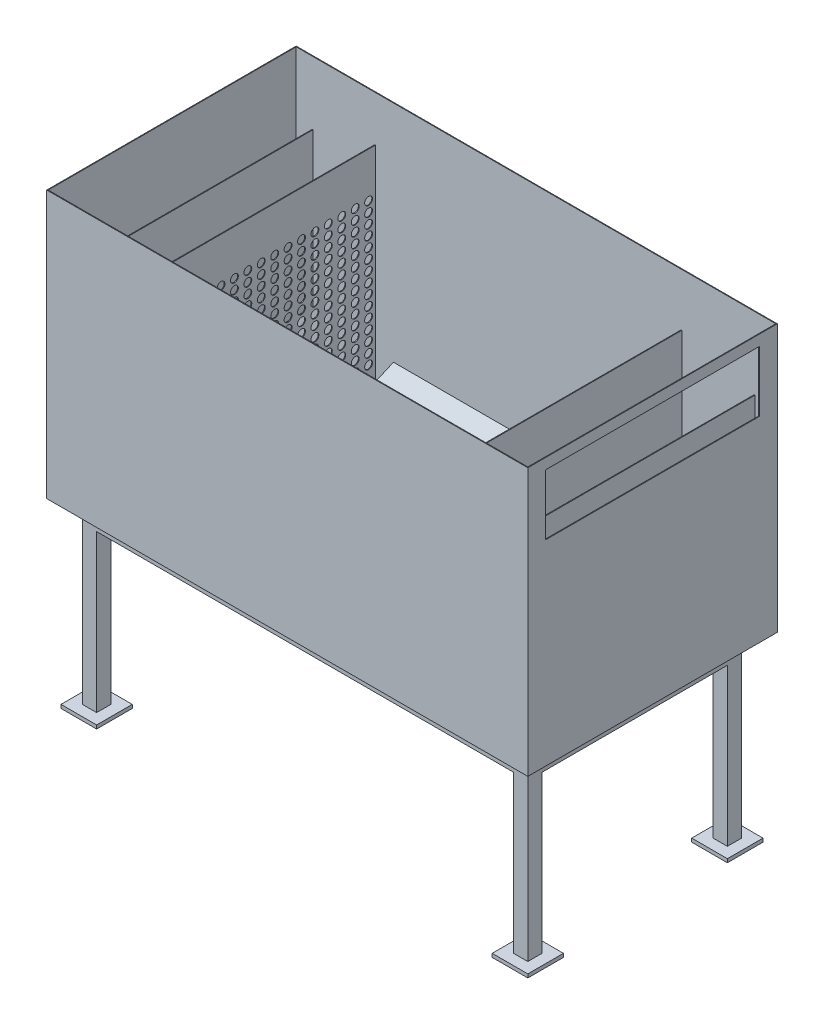
SolidWorks part; units mm, degrees
ref_plane "Спереди" through (0, 0, 0) normal (0, 0, 1) x (1, 0, 0)
ref_plane "Сверху" through (0, 0, 0) normal (0, 1, 0) x (1, 0, 0)
ref_plane "Справа" through (0, 0, 0) normal (1, 0, 0) x (0, 0, -1)
sketch "MASTER_FOOTPRINT" plane through (0, 0, 0) normal (0, 1, 0) x (1, 0, 0)
  line L1 (0, 0) -> (1350, 0)
  line L2 (0, 0) -> (0, 700)
  line L3 (0, 700) -> (1350, 700)
  line L4 (1350, 0) -> (1350, 700)
  dimension "D1" = 1350
  dimension "D2" = 700
extrude "BATH_BASE_PLATE" add sketch "MASTER_FOOTPRINT" along normal blind 750
shell "BATH_SHELL_2MM" thickness 2 removed face at (675, 750, -350)
sketch "Эскиз1" plane through (0, 0, 0) normal (1, 0, 0) x (0, 0, -1)
  circle A0 centre (350, 420) radius 50
extrude "INLET_D100_OPENING" cut sketch "Эскиз1" along normal blind 10
sketch "Эскиз2" plane through (0, 0, 0) normal (1, 0, 0) x (0, 0, -1)
  line L1 (80, 220) -> (620, 220)
  line L2 (80, 220) -> (80, 650)
  line L3 (80, 650) -> (620, 650)
  line L4 (620, 220) -> (620, 650)
extrude "INLET_IMPACT_BAFFLE" add sketch "Эскиз2" along normal blind 2 from offset 125 separate body
sketch "Эскиз3" plane through (0, 0, 0) normal (1, 0, 0) x (0, 0, -1)
  line L1 (30, 2) -> (670, 2)
  line L2 (30, 2) -> (30, 650)
  line L3 (30, 650) -> (670, 650)
  line L4 (670, 2) -> (670, 650)
  circle A0 centre (48.8235, 125) radius 11
  circle A1 centre (48.8235, 153.5) radius 11
  circle A2 centre (48.8235, 182) radius 11
  circle A3 centre (48.8235, 210.5) radius 11
  circle A4 centre (48.8235, 239) radius 11
  circle A5 centre (48.8235, 267.5) radius 11
  circle A6 centre (48.8235, 296) radius 11
  circle A7 centre (48.8235, 324.5) radius 11
  circle A8 centre (48.8235, 353) radius 11
  circle A9 centre (48.8235, 381.5) radius 11
  circle A10 centre (48.8235, 410) radius 11
  circle A11 centre (48.8235, 438.5) radius 11
  circle A12 centre (48.8235, 467) radius 11
  circle A13 centre (48.8235, 495.5) radius 11
  circle A14 centre (48.8235, 524) radius 11
  circle A15 centre (86.4706, 125) radius 11
  circle A16 centre (86.4706, 153.5) radius 11
  circle A17 centre (86.4706, 182) radius 11
  circle A18 centre (86.4706, 210.5) radius 11
  circle A19 centre (86.4706, 239) radius 11
  circle A20 centre (86.4706, 267.5) radius 11
  circle A21 centre (86.4706, 296) radius 11
  circle A22 centre (86.4706, 324.5) radius 11
  circle A23 centre (86.4706, 353) radius 11
  circle A24 centre (86.4706, 381.5) radius 11
  circle A25 centre (86.4706, 410) radius 11
  circle A26 centre (86.4706, 438.5) radius 11
  circle A27 centre (86.4706, 467) radius 11
  circle A28 centre (86.4706, 495.5) radius 11
  circle A29 centre (86.4706, 524) radius 11
  circle A30 centre (124.1176, 125) radius 11
  circle A31 centre (124.1176, 153.5) radius 11
  circle A32 centre (124.1176, 182) radius 11
  circle A33 centre (124.1176, 210.5) radius 11
  circle A34 centre (124.1176, 239) radius 11
  circle A35 centre (124.1176, 267.5) radius 11
  circle A36 centre (124.1176, 296) radius 11
  circle A37 centre (124.1176, 324.5) radius 11
  circle A38 centre (124.1176, 353) radius 11
  circle A39 centre (124.1176, 381.5) radius 11
  circle A40 centre (124.1176, 410) radius 11
  circle A41 centre (124.1176, 438.5) radius 11
  circle A42 centre (124.1176, 467) radius 11
  circle A43 centre (124.1176, 495.5) radius 11
  circle A44 centre (124.1176, 524) radius 11
  circle A45 centre (161.7647, 125) radius 11
  circle A46 centre (161.7647, 153.5) radius 11
  circle A47 centre (161.7647, 182) radius 11
  circle A48 centre (161.7647, 210.5) radius 11
  circle A49 centre (161.7647, 239) radius 11
  circle A50 centre (161.7647, 267.5) radius 11
  circle A51 centre (161.7647, 296) radius 11
  circle A52 centre (161.7647, 324.5) radius 11
  circle A53 centre (161.7647, 353) radius 11
  circle A54 centre (161.7647, 381.5) radius 11
  circle A55 centre (161.7647, 410) radius 11
  circle A56 centre (161.7647, 438.5) radius 11
  circle A57 centre (161.7647, 467) radius 11
  circle A58 centre (161.7647, 495.5) radius 11
  circle A59 centre (161.7647, 524) radius 11
  circle A60 centre (199.4118, 125) radius 11
  circle A61 centre (199.4118, 153.5) radius 11
  circle A62 centre (199.4118, 182) radius 11
  circle A63 centre (199.4118, 210.5) radius 11
  circle A64 centre (199.4118, 239) radius 11
  circle A65 centre (199.4118, 267.5) radius 11
  circle A66 centre (199.4118, 296) radius 11
  circle A67 centre (199.4118, 324.5) radius 11
  circle A68 centre (199.4118, 353) radius 11
  circle A69 centre (199.4118, 381.5) radius 11
  circle A70 centre (199.4118, 410) radius 11
  circle A71 centre (199.4118, 438.5) radius 11
  circle A72 centre (199.4118, 467) radius 11
  circle A73 centre (199.4118, 495.5) radius 11
  circle A74 centre (199.4118, 524) radius 11
  circle A75 centre (237.0588, 125) radius 11
  circle A76 centre (237.0588, 153.5) radius 11
  circle A77 centre (237.0588, 182) radius 11
  circle A78 centre (237.0588, 210.5) radius 11
  circle A79 centre (237.0588, 239) radius 11
  circle A80 centre (237.0588, 267.5) radius 11
  circle A81 centre (237.0588, 296) radius 11
  circle A82 centre (237.0588, 324.5) radius 11
  circle A83 centre (237.0588, 353) radius 11
  circle A84 centre (237.0588, 381.5) radius 11
  circle A85 centre (237.0588, 410) radius 11
  circle A86 centre (237.0588, 438.5) radius 11
  circle A87 centre (237.0588, 467) radius 11
  circle A88 centre (237.0588, 495.5) radius 11
  circle A89 centre (237.0588, 524) radius 11
  circle A90 centre (274.7059, 125) radius 11
  circle A91 centre (274.7059, 153.5) radius 11
  circle A92 centre (274.7059, 182) radius 11
  circle A93 centre (274.7059, 210.5) radius 11
  circle A94 centre (274.7059, 239) radius 11
  circle A95 centre (274.7059, 267.5) radius 11
  circle A96 centre (274.7059, 296) radius 11
  circle A97 centre (274.7059, 324.5) radius 11
  circle A98 centre (274.7059, 353) radius 11
  circle A99 centre (274.7059, 381.5) radius 11
  circle A100 centre (274.7059, 410) radius 11
  circle A101 centre (274.7059, 438.5) radius 11
  circle A102 centre (274.7059, 467) radius 11
  circle A103 centre (274.7059, 495.5) radius 11
  circle A104 centre (274.7059, 524) radius 11
  circle A105 centre (312.3529, 125) radius 11
  circle A106 centre (312.3529, 153.5) radius 11
  circle A107 centre (312.3529, 182) radius 11
  circle A108 centre (312.3529, 210.5) radius 11
  circle A109 centre (312.3529, 239) radius 11
  circle A110 centre (312.3529, 267.5) radius 11
  circle A111 centre (312.3529, 296) radius 11
  circle A112 centre (312.3529, 324.5) radius 11
  circle A113 centre (312.3529, 353) radius 11
  circle A114 centre (312.3529, 381.5) radius 11
  circle A115 centre (312.3529, 410) radius 11
  circle A116 centre (312.3529, 438.5) radius 11
  circle A117 centre (312.3529, 467) radius 11
  circle A118 centre (312.3529, 495.5) radius 11
  circle A119 centre (312.3529, 524) radius 11
  circle A120 centre (350, 125) radius 11
  circle A121 centre (350, 153.5) radius 11
  circle A122 centre (350, 182) radius 11
  circle A123 centre (350, 210.5) radius 11
  circle A124 centre (350, 239) radius 11
  circle A125 centre (350, 267.5) radius 11
  circle A126 centre (350, 296) radius 11
  circle A127 centre (350, 324.5) radius 11
  circle A128 centre (350, 353) radius 11
  circle A129 centre (350, 381.5) radius 11
  circle A130 centre (350, 410) radius 11
  circle A131 centre (350, 438.5) radius 11
  circle A132 centre (350, 467) radius 11
  circle A133 centre (350, 495.5) radius 11
  circle A134 centre (350, 524) radius 11
  circle A135 centre (387.6471, 125) radius 11
  circle A136 centre (387.6471, 153.5) radius 11
  circle A137 centre (387.6471, 182) radius 11
  circle A138 centre (387.6471, 210.5) radius 11
  circle A139 centre (387.6471, 239) radius 11
  circle A140 centre (387.6471, 267.5) radius 11
  circle A141 centre (387.6471, 296) radius 11
  circle A142 centre (387.6471, 324.5) radius 11
  circle A143 centre (387.6471, 353) radius 11
  circle A144 centre (387.6471, 381.5) radius 11
  circle A145 centre (387.6471, 410) radius 11
  circle A146 centre (387.6471, 438.5) radius 11
  circle A147 centre (387.6471, 467) radius 11
  circle A148 centre (387.6471, 495.5) radius 11
  circle A149 centre (387.6471, 524) radius 11
  circle A150 centre (425.2941, 125) radius 11
  circle A151 centre (425.2941, 153.5) radius 11
  circle A152 centre (425.2941, 182) radius 11
  circle A153 centre (425.2941, 210.5) radius 11
  circle A154 centre (425.2941, 239) radius 11
  circle A155 centre (425.2941, 267.5) radius 11
  circle A156 centre (425.2941, 296) radius 11
  circle A157 centre (425.2941, 324.5) radius 11
  circle A158 centre (425.2941, 353) radius 11
  circle A159 centre (425.2941, 381.5) radius 11
  circle A160 centre (425.2941, 410) radius 11
  circle A161 centre (425.2941, 438.5) radius 11
  circle A162 centre (425.2941, 467) radius 11
  circle A163 centre (425.2941, 495.5) radius 11
  circle A164 centre (425.2941, 524) radius 11
  circle A165 centre (462.9412, 125) radius 11
  circle A166 centre (462.9412, 153.5) radius 11
  circle A167 centre (462.9412, 182) radius 11
  circle A168 centre (462.9412, 210.5) radius 11
  circle A169 centre (462.9412, 239) radius 11
  circle A170 centre (462.9412, 267.5) radius 11
  circle A171 centre (462.9412, 296) radius 11
  circle A172 centre (462.9412, 324.5) radius 11
  circle A173 centre (462.9412, 353) radius 11
  circle A174 centre (462.9412, 381.5) radius 11
  circle A175 centre (462.9412, 410) radius 11
  circle A176 centre (462.9412, 438.5) radius 11
  circle A177 centre (462.9412, 467) radius 11
  circle A178 centre (462.9412, 495.5) radius 11
  circle A179 centre (462.9412, 524) radius 11
  circle A180 centre (500.5882, 125) radius 11
  circle A181 centre (500.5882, 153.5) radius 11
  circle A182 centre (500.5882, 182) radius 11
  circle A183 centre (500.5882, 210.5) radius 11
  circle A184 centre (500.5882, 239) radius 11
  circle A185 centre (500.5882, 267.5) radius 11
  circle A186 centre (500.5882, 296) radius 11
  circle A187 centre (500.5882, 324.5) radius 11
  circle A188 centre (500.5882, 353) radius 11
  circle A189 centre (500.5882, 381.5) radius 11
  circle A190 centre (500.5882, 410) radius 11
  circle A191 centre (500.5882, 438.5) radius 11
  circle A192 centre (500.5882, 467) radius 11
  circle A193 centre (500.5882, 495.5) radius 11
  circle A194 centre (500.5882, 524) radius 11
  circle A195 centre (538.2353, 125) radius 11
  circle A196 centre (538.2353, 153.5) radius 11
  circle A197 centre (538.2353, 182) radius 11
  circle A198 centre (538.2353, 210.5) radius 11
  circle A199 centre (538.2353, 239) radius 11
  circle A200 centre (538.2353, 267.5) radius 11
  circle A201 centre (538.2353, 296) radius 11
  circle A202 centre (538.2353, 324.5) radius 11
  circle A203 centre (538.2353, 353) radius 11
  circle A204 centre (538.2353, 381.5) radius 11
  circle A205 centre (538.2353, 410) radius 11
  circle A206 centre (538.2353, 438.5) radius 11
  circle A207 centre (538.2353, 467) radius 11
  circle A208 centre (538.2353, 495.5) radius 11
  circle A209 centre (538.2353, 524) radius 11
  circle A210 centre (575.8824, 125) radius 11
  circle A211 centre (575.8824, 153.5) radius 11
  circle A212 centre (575.8824, 182) radius 11
  circle A213 centre (575.8824, 210.5) radius 11
  circle A214 centre (575.8824, 239) radius 11
  circle A215 centre (575.8824, 267.5) radius 11
  circle A216 centre (575.8824, 296) radius 11
  circle A217 centre (575.8824, 324.5) radius 11
  circle A218 centre (575.8824, 353) radius 11
  circle A219 centre (575.8824, 381.5) radius 11
  circle A220 centre (575.8824, 410) radius 11
  circle A221 centre (575.8824, 438.5) radius 11
  circle A222 centre (575.8824, 467) radius 11
  circle A223 centre (575.8824, 495.5) radius 11
  circle A224 centre (575.8824, 524) radius 11
  circle A225 centre (613.5294, 125) radius 11
  circle A226 centre (613.5294, 153.5) radius 11
  circle A227 centre (613.5294, 182) radius 11
  circle A228 centre (613.5294, 210.5) radius 11
  circle A229 centre (613.5294, 239) radius 11
  circle A230 centre (613.5294, 267.5) radius 11
  circle A231 centre (613.5294, 296) radius 11
  circle A232 centre (613.5294, 324.5) radius 11
  circle A233 centre (613.5294, 353) radius 11
  circle A234 centre (613.5294, 381.5) radius 11
  circle A235 centre (613.5294, 410) radius 11
  circle A236 centre (613.5294, 438.5) radius 11
  circle A237 centre (613.5294, 467) radius 11
  circle A238 centre (613.5294, 495.5) radius 11
  circle A239 centre (613.5294, 524) radius 11
  circle A240 centre (651.1765, 125) radius 11
  circle A241 centre (651.1765, 153.5) radius 11
  circle A242 centre (651.1765, 182) radius 11
  circle A243 centre (651.1765, 210.5) radius 11
  circle A244 centre (651.1765, 239) radius 11
  circle A245 centre (651.1765, 267.5) radius 11
  circle A246 centre (651.1765, 296) radius 11
  circle A247 centre (651.1765, 324.5) radius 11
  circle A248 centre (651.1765, 353) radius 11
  circle A249 centre (651.1765, 381.5) radius 11
  circle A250 centre (651.1765, 410) radius 11
  circle A251 centre (651.1765, 438.5) radius 11
  circle A252 centre (651.1765, 467) radius 11
  circle A253 centre (651.1765, 495.5) radius 11
  circle A254 centre (651.1765, 524) radius 11
extrude "DISTRIBUTOR_D22" add sketch "Эскиз3" along normal blind 2 from offset 250 separate body
sketch "Эскиз4" plane through (0, 0, 0) normal (1, 0, 0) x (0, 0, -1)
  line L1 (50, 320) -> (650, 320)
  line L2 (50, 320) -> (50, 650)
  line L3 (50, 650) -> (650, 650)
  line L4 (650, 320) -> (650, 650)
extrude "OUTLET_SUBMERGED_BAFFLE" add sketch "Эскиз4" along normal blind 2 from offset 1130 separate body
sketch "Эскиз5" plane through (0, 0, 0) normal (1, 0, 0) x (0, 0, -1)
  line L1 (5, 2) -> (695, 2)
  line L2 (5, 2) -> (5, 550)
  line L3 (5, 550) -> (695, 550)
  line L4 (695, 2) -> (695, 550)
extrude "OVERFLOW_WEIR_Z550" add sketch "Эскиз5" along normal blind 2 from offset 1290 separate body
sketch "Эскиз6" plane through (0, 0, 0) normal (1, 0, 0) x (0, 0, -1)
  line L1 (50, 550) -> (650, 550)
  line L2 (50, 550) -> (50, 720)
  line L3 (50, 720) -> (650, 720)
  line L4 (650, 550) -> (650, 720)
extrude "OUTLET_WEIR_SLOT_W600" cut sketch "Эскиз6" along normal blind 10 from offset 1345
sketch "Эскиз7" plane through (0, 0, 0) normal (1, 0, 0) x (0, 0, -1)
  line L0 (2, -1) -> (2, 120)
  line L1 (2, 120) -> (280, -1)
  line L2 (280, -1) -> (2, -1)
  line L3 (698, -1) -> (698, 120)
  line L4 (698, 120) -> (420, -1)
  line L5 (420, -1) -> (698, -1)
extrude "SLOPED_SEDIMENT_FLOOR" add sketch "Эскиз7" along normal blind 825 from offset 275
sketch3d "SCREW_AXIS_30DEG_REFERENCE"
  line L0 (400, 70, -350) -> (1450, 676.2178, -350)
sketch "Эскиз8" plane through (0, 0, 0) normal (0, 1, 0) x (1, 0, 0)
  line L1 (50, 50) -> (90, 50)
  line L2 (50, 50) -> (50, 90)
  line L3 (50, 90) -> (90, 90)
  line L4 (90, 50) -> (90, 90)
  line L6 (50, 610) -> (90, 610)
  line L7 (50, 610) -> (50, 650)
  line L8 (50, 650) -> (90, 650)
  line L9 (90, 610) -> (90, 650)
  line L11 (1260, 50) -> (1300, 50)
  line L12 (1260, 50) -> (1260, 90)
  line L13 (1260, 90) -> (1300, 90)
  line L14 (1300, 50) -> (1300, 90)
  line L16 (1260, 610) -> (1300, 610)
  line L17 (1260, 610) -> (1260, 650)
  line L18 (1260, 650) -> (1300, 650)
  line L19 (1300, 610) -> (1300, 650)
extrude "FRAME_LEGS_40X40_H500" add sketch "Эскиз8" against normal blind 500
sketch "Эскиз9" plane through (0, 0, 0) normal (0, 1, 0) x (1, 0, 0)
  line L1 (50, 50) -> (1300, 50)
  line L2 (50, 50) -> (50, 90)
  line L3 (50, 90) -> (1300, 90)
  line L4 (1300, 50) -> (1300, 90)
  line L6 (50, 610) -> (1300, 610)
  line L7 (50, 610) -> (50, 650)
  line L8 (50, 650) -> (1300, 650)
  line L9 (1300, 610) -> (1300, 650)
extrude "FRAME_LONGITUDINAL_RAILS" add sketch "Эскиз9" against normal blind 40 from offset 20 offset against normal yes
sketch "Эскиз10" plane through (0, 0, 0) normal (0, 1, 0) x (1, 0, 0)
  line L1 (50, 90) -> (90, 90)
  line L2 (50, 90) -> (50, 610)
  line L3 (50, 610) -> (90, 610)
  line L4 (90, 90) -> (90, 610)
  line L6 (1260, 90) -> (1300, 90)
  line L7 (1260, 90) -> (1260, 610)
  line L8 (1260, 610) -> (1300, 610)
  line L9 (1300, 90) -> (1300, 610)
extrude "FRAME_TRANSVERSE_RAILS" add sketch "Эскиз10" against normal blind 40 from offset 20 offset against normal yes
sketch "Эскиз11" plane through (0, 0, 0) normal (0, 1, 0) x (1, 0, 0)
  line L1 (20, 20) -> (120, 20)
  line L2 (20, 20) -> (20, 120)
  line L3 (20, 120) -> (120, 120)
  line L4 (120, 20) -> (120, 120)
  line L6 (20, 580) -> (120, 580)
  line L7 (20, 580) -> (20, 680)
  line L8 (20, 680) -> (120, 680)
  line L9 (120, 580) -> (120, 680)
  line L11 (1230, 20) -> (1330, 20)
  line L12 (1230, 20) -> (1230, 120)
  line L13 (1230, 120) -> (1330, 120)
  line L14 (1330, 20) -> (1330, 120)
  line L16 (1230, 580) -> (1330, 580)
  line L17 (1230, 580) -> (1230, 680)
  line L18 (1230, 680) -> (1330, 680)
  line L19 (1330, 580) -> (1330, 680)
extrude "FRAME_FOOT_PADS_100X100" add sketch "Эскиз11" against normal blind 10 from offset 500 offset against normal yes
equation "\"AI_Q_Peak\"= 0.006"
equation "\"AI_B_Bath\"= 700"
equation "\"AI_L_Settle\"= 900"
equation "\"AI_L_Inlet\"= 250"
equation "\"AI_L_Outlet\"= 200"
equation "\"AI_L_Bath\"= 1350"
equation "\"AI_H_Water\"= 550"
equation "\"AI_H_Freeboard\"= 200"
equation "\"AI_H_Bath\"= 750"
equation "\"AI_Shell_Thickness\"= 2"
equation "\"AI_Inlet_DN\"= 100"
equation "\"AI_Weir_Width\"= 600"
equation "\"AI_Inlet_Baffle_Offset\"= 125"
equation "\"AI_Distributor_Open_Area\"= 0.28"
equation "\"AI_Distributor_Hole_Dia\"= 22"
equation "\"AI_Distributor_Blind_Zone\"= 110"
equation "\"AI_Outlet_Baffle_Depth\"= 250"
equation "\"AI_Screw_Diameter\"= 100"
equation "\"AI_Screw_Pitch\"= 100"
equation "\"AI_Screw_Angle\"= 30"
equation "\"AI_Screw_Rpm\"= 15"
equation "\"AI_Screw_Clearance\"= 5"
equation "\"AI_Liner_Thickness\"= 5"
equation "\"AI_Discharge_Height\"= 650"
equation "\"AI_Frame_Height\"= 500"
equation "\"D1@MASTER_FOOTPRINT\" = \"AI_L_Bath\""
equation "\"D2@MASTER_FOOTPRINT\" = \"AI_B_Bath\""
equation "\"D1@BATH_BASE_PLATE\" = \"AI_H_Bath\""
